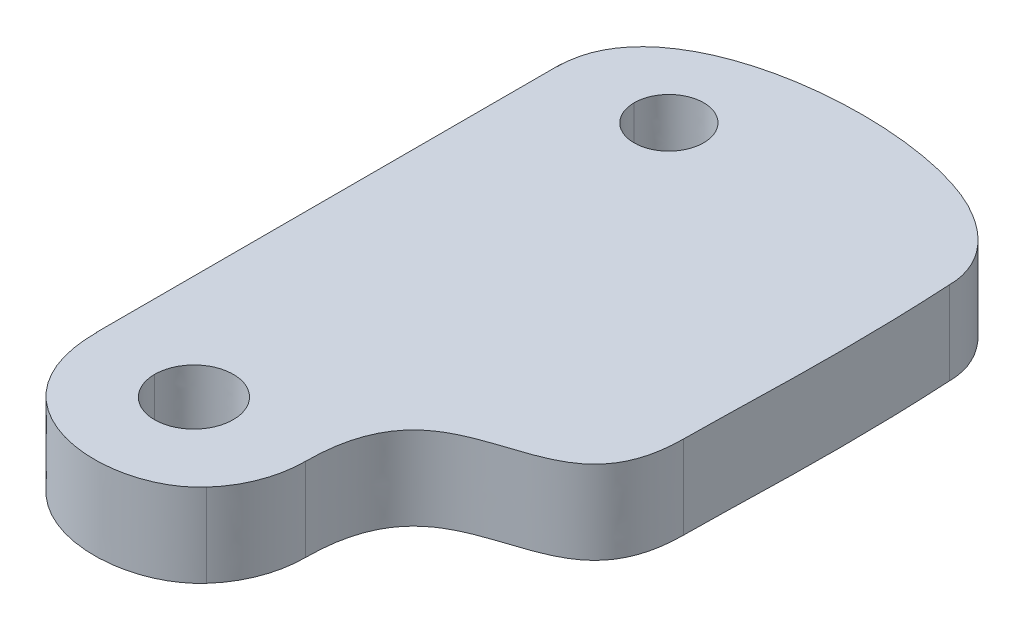
SolidWorks part; units mm, degrees
material "Acrylic (Medium-high impact)"
ref_plane "Front Plane" through (0, 0, 0) normal (0, 0, 1) x (1, 0, 0)
ref_plane "Top Plane" through (0, 0, 0) normal (0, 1, 0) x (1, 0, 0)
ref_plane "Right Plane" through (0, 0, 0) normal (1, 0, 0) x (0, 0, -1)
sketch "Sketch1" plane through (0, 0, 0) normal (0, 1, 0) x (1, 0, 0)
  line L0 (-7.396, 7.8615) -> (-7.4061, 8.0473)
  line L1 (-7.4061, 8.0473) -> (-7.4061, -9.6675)
  line L2 (-7.4061, -9.6675) -> (-7.396, -9.6675)
  spline S0 degree 3 poles (-7.396, -9.6675) (-7.4195, -14.3593) (-2.0973, -14.8248) (-0.2024, -12.6881) knots 3 3 3 3 4 4 4 4
  spline S1 degree 3 poles (-0.2024, -12.6881) (0.4612, -11.9627) (0.8342, -10.9791) (0.8342, -9.9533) knots 4 4 4 4 5 5 5 5
  spline S2 degree 3 poles (0.8342, -9.9533) (0.8476, -3.7592) (7.2767, -7.4622) (7.2998, -2.009) knots 5 5 5 5 6 6 6 6
  spline S3 degree 3 poles (7.2998, -2.009) (7.31, 0.4563) (7.5237, 3.7521) (7.2767, 8.1473) knots 6 6 6 6 7 7 7 7
  spline S4 degree 3 poles (7.2767, 8.1473) (7.2767, 9.1731) (6.6117, 10.157) (5.4288, 10.8822) knots 7 7 7 7 8 8 8 8
  spline S5 degree 3 poles (5.4288, 10.8822) (2.0508, 13.0189) (-7.4378, 12.5533) (-7.396, 7.8615) knots 8 8 8 8 9 9 9 9
  spline S6 degree 3 poles (-4.7359, 8.1473) (-4.7359, 8.879) (-4.1437, 9.4723) (-3.4134, 9.4723) (-2.6828, 9.4723) (-2.0906, 8.879) (-2.0906, 8.1473) knots 2 2 2 2 3 3 3 4 4 4 4
  spline S7 degree 3 poles (-2.0906, 8.1473) (-2.0906, 7.4156) (-2.6828, 6.8221) (-3.4132, 6.8221) (-4.1437, 6.8221) (-4.7359, 7.4156) (-4.7359, 8.1473) knots 0 0 0 0 1 1 1 2 2 2 2
  spline S8 degree 3 poles (-3.4132, -11.4535) (-2.5863, -11.4535) (-1.9158, -10.7817) (-1.9158, -9.9533) knots 3 3 3 3 4 4 4 4
  spline S9 degree 3 poles (-4.9105, -9.9531) (-4.9107, -10.7817) (-4.2401, -11.4533) (-3.4132, -11.4535) knots 2 2 2 2 3 3 3 3
  spline S10 degree 3 poles (-1.9158, -9.9533) (-1.9158, -9.1248) (-2.5863, -8.453) (-3.4132, -8.453) (-4.2401, -8.453) (-4.9105, -9.1248) (-4.9105, -9.9531) knots 0 0 0 0 1 1 1 2 2 2 2
extrude "Boss-Extrude1" add sketch "Sketch1" along normal blind 3.175
